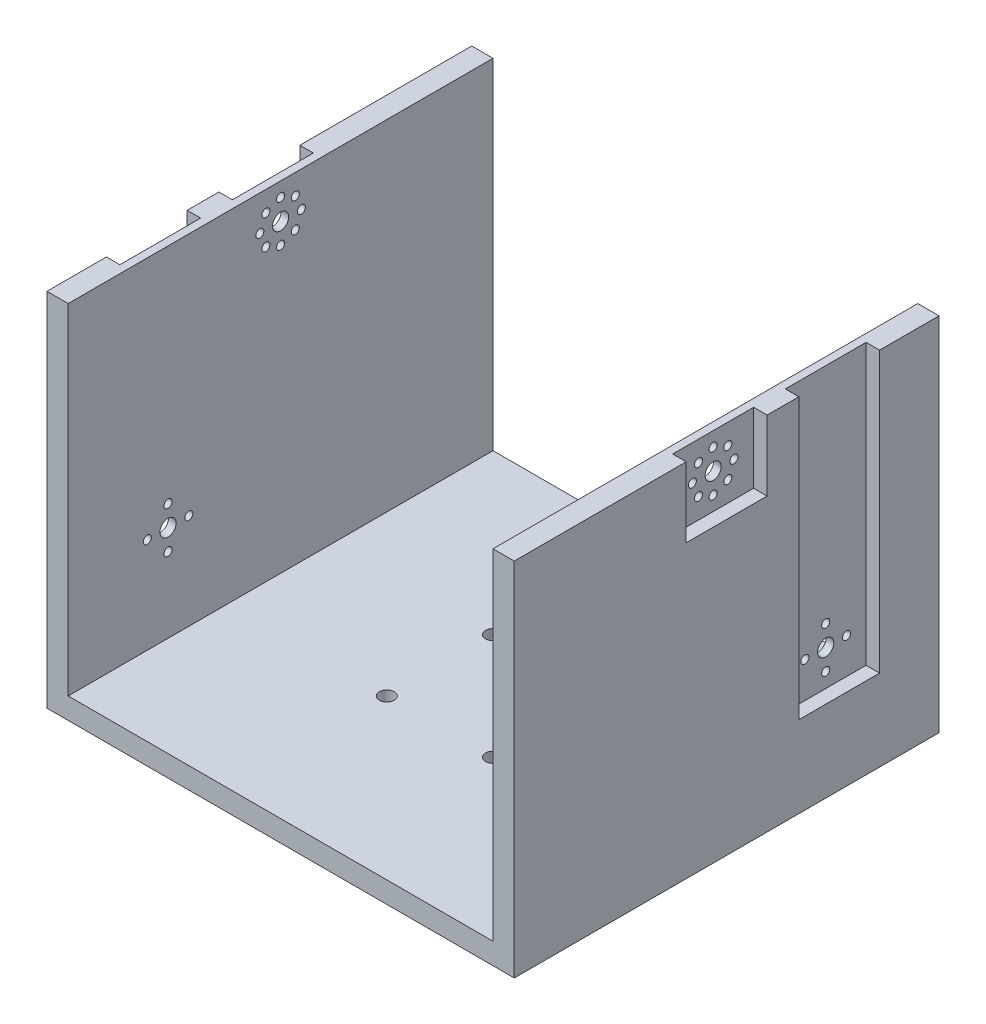
SolidWorks part; units mm, degrees
ref_plane "Front" through (0, 0, 0) normal (0, 0, 1) x (1, 0, 0)
ref_plane "Top" through (0, 0, 0) normal (0, 1, 0) x (1, 0, 0)
ref_plane "Right" through (0, 0, 0) normal (1, 0, 0) x (0, 0, -1)
sketch "Sketch2" plane through (0, 0, 0) normal (0, 1, 0) x (1, 0, 0)
  line L0 (0, 0) -> (0, -100) construction
  line L1 (-100, -100) -> (100, -100)
  line L2 (-100, -100) -> (-100, 100)
  line L3 (-100, 100) -> (100, 100)
  line L4 (100, -100) -> (100, 100)
  line L5 (0, 0) -> (-100, 0) construction
  point P0 (0, 0)
  dimension "D1" = 200
  dimension "D2" = 200
extrude "Boss-Extrude1" add sketch "Sketch2" along normal blind 10
sketch "Sketch3" plane through (0, 0, 0) normal (0, 1, 0) x (1, 0, 0)
  line L0 (-100, -100) -> (100, -100) construction
  line L1 (-100, 100) -> (-110, 100)
  line L2 (-100, 100) -> (-100, -100)
  line L3 (-100, -100) -> (-110, -100)
  line L4 (-110, 100) -> (-110, -100)
  line L5 (0, 0) -> (0, 100) construction
  line L6 (100, 100) -> (-100, 100) construction
  line L7 (110, 100) -> (110, -100)
  line L8 (100, -100) -> (110, -100)
  line L9 (100, 100) -> (100, -100)
  line L10 (100, 100) -> (110, 100)
  dimension "D1" = 10
extrude "Boss-Extrude2" add sketch "Sketch3" along normal blind 170
sketch "Sketch4" plane through (0, 10, 0) normal (0, 1, 0) x (1, 0, 0)
  point P4 (0, 0)
hole_wizard "M6 Clearance Hole1" positions "Sketch5" profile "Sketch6" hole size "M6" standard "ANSI Metric" end condition up to next
sketch "Sketch5" plane through (0, 10, 0) normal (0, 1, 0) x (1, 0, 0)
  line L0 (0, 0) -> (0, 25) construction
  line L1 (0, 25) -> (-25, 25) construction
  line L3 (0, 25) -> (25, 25) construction
  point P0 (-25, 25)
  point P13 (25, 25)
  point P14 (25, -25)
  point P15 (-25, -25)
  dimension "D1" = 25
  dimension "D2" = 4
sketch "Sketch6" plane through (-25, 10, -25) normal (1, 0, 0) x (0, 0, 1)
  line L0 (0, 0) -> (0, 10)
  line L1 (0, 10) -> (3.5, 10)
  line L2 (3.5, 10) -> (3.5, 0)
  line L5 (3.5, 0) -> (0, 0)
  line L11 (0, -6.35) -> (0, 107.95) construction
  dimension "Thru Hole Dia." = 7
  dimension "Thru Hole Depth" = 10
sketch "Sketch7" plane through (100, 0, 0) normal (-1, 0, 0) x (0, 0, 1)
  line L0 (-100, 170) -> (100, 170) construction
  line L1 (0, 153.49) -> (0, 163.269) construction
  line L2 (0, 153.49) -> (0, 163.269) construction
  circle A0 centre (0, 153.49) radius 3.81
  circle A1 centre (0, 163.269) radius 1.8987
  circle A2 centre (6.9148, 160.4048) radius 1.8987
  circle A3 centre (9.779, 153.49) radius 1.8987
  circle A4 centre (6.9148, 146.5752) radius 1.8987
  circle A5 centre (0, 143.711) radius 1.8987
  circle A6 centre (-6.9148, 146.5752) radius 1.8987
  circle A7 centre (-9.779, 153.49) radius 1.8987
  circle A8 centre (-6.9148, 160.4048) radius 1.8987
  point P7 (0, 170)
  dimension "D1" = 7.62
  dimension "D3" = 3.7973
  dimension "D2" = 16.51
  dimension "D6" = 9.779
  dimension "D5" = 8
extrude "Cut-Extrude1" cut sketch "Sketch7" against normal through all both and the other way through all
sketch "Sketch8" plane through (0, 170, 0) normal (0, 1, 0) x (1, 0, 0)
  line L1 (103.65, -19.05) -> (110, -19.05)
  line L2 (103.65, -19.05) -> (103.65, 19.05)
  line L3 (103.65, 19.05) -> (110, 19.05)
  line L4 (110, -19.05) -> (110, 19.05)
  line L5 (103.65, -19.05) -> (110, 19.05) construction
  line L6 (103.65, 19.05) -> (110, -19.05) construction
  line L9 (110, -100) -> (110, 100) construction
  line L10 (0, 0) -> (0, 100) construction
  line L11 (100, 100) -> (-100, 100) construction
  line L13 (-103.65, 19.05) -> (-110, -19.05) construction
  line L14 (-103.65, -19.05) -> (-110, 19.05) construction
  line L16 (-110, -19.05) -> (-110, 19.05)
  line L17 (-103.65, 19.05) -> (-110, 19.05)
  line L18 (-103.65, -19.05) -> (-103.65, 19.05)
  line L19 (-103.65, -19.05) -> (-110, -19.05)
  point P0 (106.825, 0)
  point P12 (110, 0)
  point P23 (-106.825, 0)
  dimension "D1" = 38.1
  dimension "D2" = 6.35
extrude "Cut-Extrude2" cut sketch "Sketch8" against normal blind 33.02
sketch "Sketch9" plane through (110, 0, 0) normal (1, 0, 0) x (0, 0, -1)
  line L0 (36.4814, 38.3278) -> (42.5774, 38.3278) construction
  line L2 (72.0014, 71.8658) -> (72.0014, 38.3178)
  line L3 (72.0014, 38.3178) -> (33.9814, 38.3178)
  line L4 (33.9814, 71.8658) -> (33.9814, 38.3178)
  line L5 (72.0014, 71.8658) -> (33.9814, 38.3178) construction
  line L6 (72.0014, 38.3178) -> (33.9814, 71.8658) construction
  line L7 (36.4814, 47.4718) -> (36.4814, 38.3278) construction
  line L13 (72.0014, 71.8658) -> (72.0014, 170)
  line L14 (19.05, 170) -> (100, 170) construction
  line L15 (72.0014, 170) -> (33.9814, 170)
  line L16 (33.9814, 170) -> (33.9814, 71.8658)
  point P0 (52.9914, 55.0918)
  point P10 (52.9914, 64.8708)
  point P11 (43.2124, 55.0918)
  point P13 (52.9914, 45.3128)
  point P15 (62.7704, 55.0918)
  dimension "D1" = 0.01
  dimension "D2" = 2.5
extrude "Cut-Extrude3" cut sketch "Sketch9" against normal blind 6.35
sketch "Sketch11" plane through (103.65, 0, 0) normal (1, 0, 0) x (0, 0, -1)
  circle A0 centre (52.9914, 55.0918) radius 3.81
  circle A1 centre (0, 153.49) radius 3.81 construction
extrude "Cut-Extrude4" cut sketch "Sketch11" against normal up to next
hole_wizard "#6 Clearance Hole1" positions "Sketch12" profile "Sketch13" hole size "#6" standard "ANSI Inch" end condition up to next
sketch "Sketch12" plane through (103.65, 0, 0) normal (1, 0, 0) x (0, 0, -1)
  point P0 (52.9914, 64.8708)
  point P3 (43.2124, 55.0918)
  point P6 (62.7704, 55.0918)
  point P10 (52.9914, 45.3128)
sketch "Sketch13" plane through (103.65, 64.8708, -52.9914) normal (0, 1, 0) x (0, 0, -1)
  line L0 (0, 0) -> (0, 3.65)
  line L1 (0, 3.65) -> (1.8986, 3.65)
  line L2 (1.8986, 3.65) -> (1.8986, 0)
  line L5 (1.8986, 0) -> (0, 0)
  line L11 (0, -6.35) -> (0, 107.95) construction
  dimension "Thru Hole Dia." = 3.7973
  dimension "Thru Hole Depth" = 3.65
ref_plane "Plane1" through (0, 0, 0) normal (-0.7071, 0, 0.7071) x (0.7071, 0, 0.7071)
ref_axis "Axis1" through (0, 0, 0) along (0, 1, 0)
pattern_circular "CirPattern1" count 2 over 360 about axis through (0, 0, 0) along (0, 1, 0) of "Cut-Extrude3", "Cut-Extrude4", "#6 Clearance Hole1"
sketch "Esquisse1" plane through (0, 10, 0) normal (0, 1, 0) x (1, 0, 0)
  circle A0 centre (53, 81.9759) radius 3.175
  circle A1 centre (53, -18.5603) radius 3.175
  dimension "D1" = 6.35
  dimension "D2" = 6.35
extrude "Enlèv. mat.-Extru.1" cut sketch "Esquisse1" against normal up to next
equation "\"Longueur\"= 200"
equation "\"D2@Sketch2\"=\"Longueur\""
equation "\"Largeur\"=200"
equation "\"D1@Sketch2\"=\"Largeur\""
